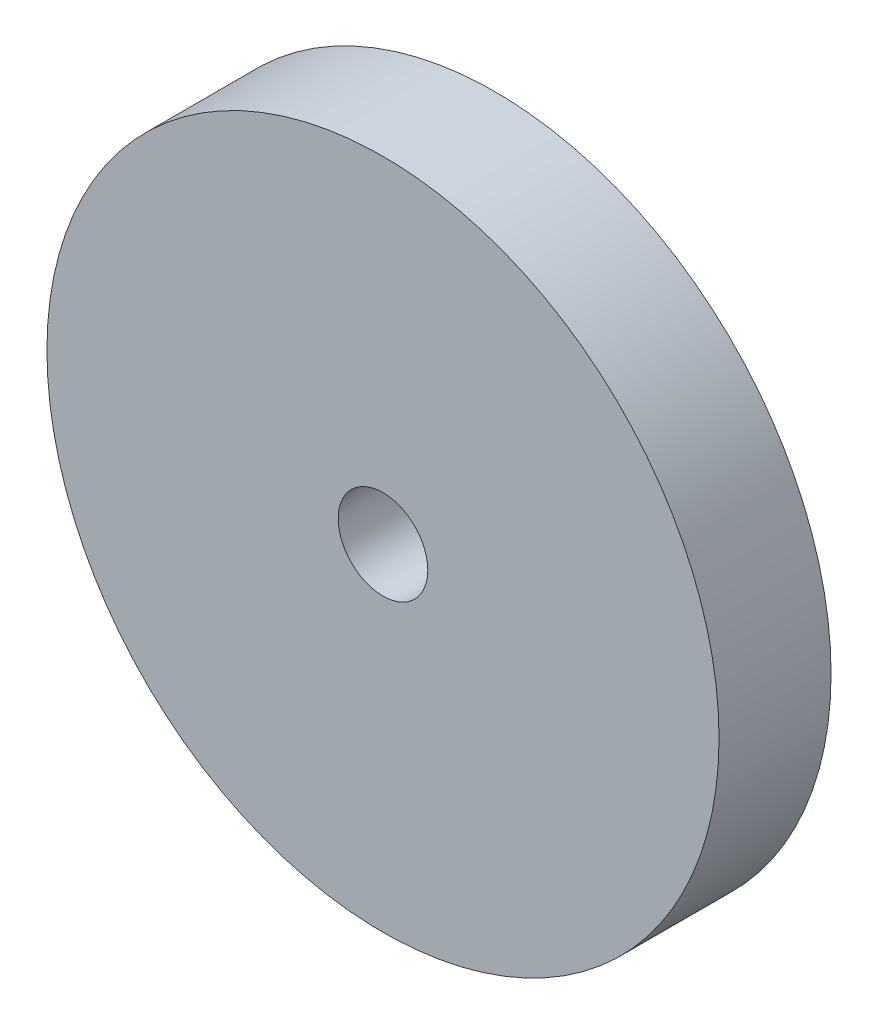
SolidWorks part; units mm, degrees
ref_plane "Front Plane" through (0, 0, 0) normal (0, 0, 1) x (1, 0, 0)
ref_plane "Top Plane" through (0, 0, 0) normal (0, 1, 0) x (1, 0, 0)
ref_plane "Right Plane" through (0, 0, 0) normal (1, 0, 0) x (0, 0, -1)
sketch "Sketch1" plane through (0, 0, 0) normal (0, 0, 1) x (1, 0, 0)
  circle A0 centre (0, 0) radius 15
  dimension "D1" = 30
extrude "Boss-Extrude1" add sketch "Sketch1" along normal mid plane 5 contours A0
sketch "Sketch2" plane through (0, 0, 2.5) normal (0, 0, 1) x (1, 0, 0)
  circle A0 centre (0, 0) radius 2
  dimension "D1" = 4
extrude "Cut-Extrude1" cut sketch "Sketch2" against normal up to surface (5 mm away) up to face at (15, 0, -2.5)
